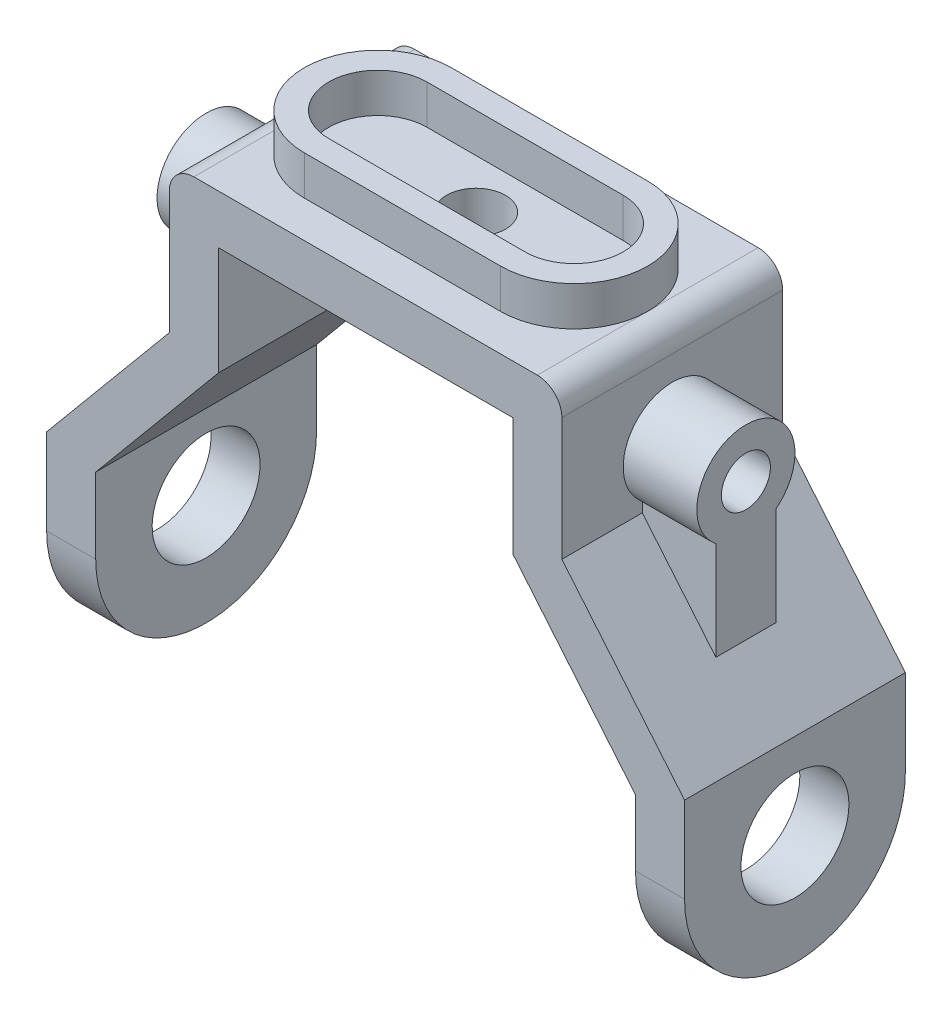
SolidWorks part; units mm, degrees
ref_plane "Front Plane" through (0, 0, 0) normal (0, 0, 1) x (1, 0, 0)
ref_plane "Top Plane" through (0, 0, 0) normal (0, 1, 0) x (1, 0, 0)
ref_plane "Right Plane" through (0, 0, 0) normal (1, 0, 0) x (0, 0, -1)
sketch "Sketch3" plane through (0, 0, 0) normal (0, 1, 0) x (1, 0, 0)
  line L1 (-65, -22.5) -> (65, -22.5)
  line L2 (-65, -22.5) -> (-65, 22.5)
  line L3 (-65, 22.5) -> (65, 22.5)
  line L4 (65, -22.5) -> (65, 22.5)
  line L5 (-65, -22.5) -> (65, 22.5) construction
  line L6 (-65, 22.5) -> (65, -22.5) construction
  point P0 (0, 0)
  dimension "D1" = 130
  dimension "D2" = 45
extrude "Boss-Extrude1" add sketch "Sketch3" against normal blind 100
sketch "Sketch5" plane through (0, 0, 0) normal (0, 0, 1) x (1, 0, 0)
  line L0 (-40, 0) -> (40, 0)
  line L1 (-65, 0) -> (65, 0) construction
  line L2 (-40, 0) -> (-40, -30)
  line L3 (-40, -30) -> (-65, -60)
  line L4 (-65, -100) -> (-65, 0) construction
  line L5 (-65, -60) -> (-65, -100)
  line L6 (-65, 0) -> (-40, 0)
  line L7 (40, 0) -> (40, -30)
  line L8 (40, -30) -> (65, -60)
  line L9 (65, -100) -> (65, 0) construction
  line L10 (65, -60) -> (65, -100)
  line L11 (65, -100) -> (65, 0)
  line L12 (65, 0) -> (40, 0)
  line L13 (-65, 0) -> (-65, -60)
  point P4 (0, 0)
  dimension "D2" = 30
  dimension "D1" = 80
  dimension "D3" = 30
  dimension "D4" = 40
  dimension "D5" = 40
extrude "Cut-Extrude1" cut sketch "Sketch5" against normal through all both and the other way through all contours L6 L13 L3 L2 | L11 L12 L7 L8 region at (53.8889, -23.3333, 0) region at (-53.8889, -23.3333, 0)
sketch "Sketch7" plane through (0, 0, 0) normal (0, 1, 0) x (1, 0, 0)
  line L0 (-20, 0) -> (20, 0) construction
  line L1 (-20, 10) -> (20, 10)
  line L2 (-20, -10) -> (20, -10)
  line L3 (-20, 0) -> (20, 0) construction
  line L4 (-20, 15) -> (20, 15)
  line L5 (-20, -15) -> (20, -15)
  arc A0 (-20, 10) -> (-20, -10) centre (-20, 0) ccw
  arc A1 (20, -10) -> (20, 10) centre (20, 0) ccw
  arc A2 (-20, 15) -> (-20, -15) centre (-20, 0) ccw
  arc A3 (20, -15) -> (20, 15) centre (20, 0) ccw
  point P2 (0, 0)
  point P10 (0, 0)
  dimension "D2" = 10
  dimension "D3" = 15
  dimension "D1" = 40
extrude "Boss-Extrude2" add sketch "Sketch7" along normal blind 8
sketch "Sketch9" plane through (0, 0, 0) normal (0, 0, 1) x (1, 0, 0)
  line L0 (-55, -100) -> (55, -100)
  line L1 (-65, -100) -> (65, -100) construction
  line L2 (55, -100) -> (55, -64.0575)
  line L3 (55, -64.0575) -> (30, -34.0575)
  line L4 (30, -34.0575) -> (30, -10)
  line L5 (30, -10) -> (-30, -10)
  line L6 (-30, -10) -> (-30, -32.1132)
  line L7 (-30, -32.1132) -> (-55, -62.1132)
  line L8 (-55, -62.1132) -> (-55, -100)
  line L9 (-65, -100) -> (-65, -60) construction
  line L10 (65, -100) -> (65, -60) construction
  line L11 (40, 0) -> (40, -30) construction
  line L12 (-40, 0) -> (-40, -30) construction
  line L13 (-20, 0) -> (20, 0) construction
  line L14 (-40, -30) -> (-65, -60) construction
  line L15 (40, -30) -> (65, -60) construction
  line L16 (-55, -100) -> (55, -100)
  dimension "D1" = 10
  dimension "D2" = 10
  dimension "D3" = 10
  dimension "D4" = 10
  dimension "D5" = 10
extrude "Cut-Extrude2" cut sketch "Sketch9" against normal through all both and the other way through all contours L7 L8 L0 L2 L3 L4 L5 L6 region at (-0.2584, -60.9446, 0)
sketch "Sketch11" plane through (0, 0, 0) normal (1, 0, 0) x (0, 0, -1)
  line L0 (-22.5, -60) -> (-22.5, -77.5)
  line L1 (0, -100) -> (22.5, -100)
  line L2 (22.5, -100) -> (22.5, -60)
  line L3 (-22.5, -77.5) -> (-22.5, -100)
  line L4 (-22.5, -100) -> (0, -100)
  arc A0 (0, -100) -> (-22.5, -77.5) centre (0, -77.5) cw
  point P10 (-22.5, -100)
  dimension "D1" = 22.5
extrude "Cut-Extrude3" cut sketch "Sketch11" against normal through all both and the other way through all contours L4 A0 L3 region at (0, -94.9742, 17.4742)
sketch "Sketch12" plane through (0, 0, 0) normal (1, 0, 0) x (0, 0, -1)
  line L0 (22.5, -77.5) -> (22.5, -100)
  line L1 (22.5, -100) -> (22.5, -60) construction
  line L2 (22.5, -100) -> (0, -100)
  circle A0 centre (0, -77.5) radius 22.5
  dimension "D1" = 45
extrude "Cut-Extrude4" cut sketch "Sketch12" against normal through all both and the other way through all contours A0 L2 L0 region at (0, -94.9742, -17.4742)
fillet "Fillet3" radius 5 2 edges at (40, 0, 0) (-40, 0, 0)
sketch "Sketch16" plane through (40, 0, 0) normal (1, 0, 0) x (0, 0, -1)
  line L0 (-6.1112, -48.0041) -> (6.1112, -48.0041)
  line L5 (6.1112, -48.0041) -> (6.1112, -27.9154)
  line L7 (-6.1112, -48.0041) -> (-6.1112, -27.9154)
  circle A0 centre (0, -20) radius 5
  circle A1 centre (0, -20) radius 10
  point P0 (0, -48.0041)
  line M6 (-22.5, -30) -> (22.5, -30)
  dimension "D2" = 10
  dimension "D3" = 20
extrude "Boss-Extrude3" add sketch "Sketch16" along normal blind 15 contours A1 A0 | A1 L5 M6 | A1 L7 M6 | L7 L0 L5 M6 region at (40, -39.0021, 0) region at (40, -29.3876, 4.6171) region at (40, -29.3876, -4.6171) region at (40, -11.2786, 4.2848)
mirror "Mirror4" about plane through (0, 0, 0) normal (1, 0, 0) of "Boss-Extrude3"
sketch "Sketch19" plane through (0, 0, 0) normal (0, 1, 0) x (1, 0, 0)
  circle A0 centre (0, 0) radius 6
  dimension "D1" = 12
extrude "Cut-Extrude5" cut sketch "Sketch19" against normal through all
sketch "Sketch23" plane through (40, 0, 0) normal (1, 0, 0) x (0, 0, -1)
  circle A0 centre (0, -20) radius 5
extrude "Cut-Extrude6" cut sketch "Sketch23" against normal through all both and the other way through all
sketch "Sketch26" plane through (0, 0, 6.1112) normal (0, 0, 1) x (1, 0, 0)
  line L0 (-40, -44.1132) -> (-40, -48.0041)
  line L1 (-40, -48.0041) -> (-43.2424, -48.0041)
  line L2 (-43.2424, -48.0041) -> (-40, -44.1132)
extrude "Cut-Extrude7" cut sketch "Sketch26" against normal blind 15
sketch "Sketch27" plane through (0, 0, 6.1112) normal (0, 0, 1) x (1, 0, 0)
  line L0 (40, -46.0575) -> (40, -48.0041)
  line L1 (40, -48.0041) -> (41.6222, -48.0041)
  line L2 (41.6222, -48.0041) -> (40, -46.0575)
extrude "Cut-Extrude8" cut sketch "Sketch27" against normal blind 15
sketch "Sketch28" plane through (65, 0, 0) normal (1, 0, 0) x (0, 0, -1)
  circle A0 centre (0, -77.5) radius 11
  dimension "D1" = 22
extrude "Cut-Extrude9" cut sketch "Sketch28" against normal through all both and the other way through all
